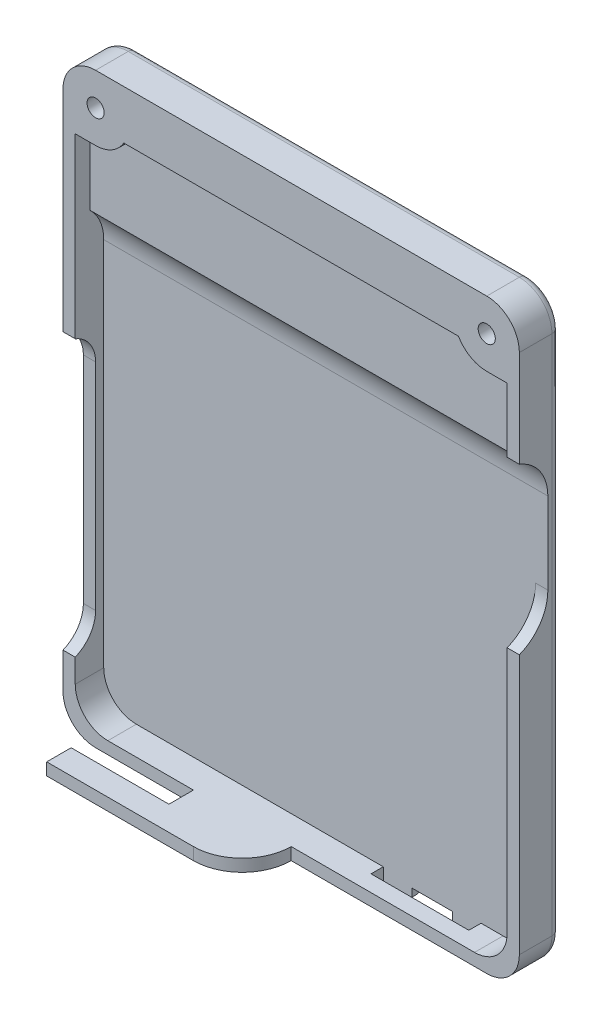
SolidWorks part; units mm, degrees
ref_plane "前视基准面" through (0, 0, 0) normal (0, 0, 1) x (1, 0, 0)
ref_plane "上视基准面" through (0, 0, 0) normal (0, 1, 0) x (1, 0, 0)
ref_plane "右视基准面" through (0, 0, 0) normal (1, 0, 0) x (0, 0, -1)
sketch "草图1" plane through (0, 0, 0) normal (0, 0, 1) x (1, 0, 0)
  line L0 (0, 0) -> (7.566, 0) construction
  line L1 (0, 0) -> (0, 23.6239) construction
  line L3 (0, 0) -> (-56, 0)
  line L4 (0, 0) -> (0, 72)
  line L5 (0, 72) -> (-56, 72)
  line L6 (-56, 0) -> (-56, 72)
  dimension "D1" = 56
  dimension "D2" = 72
extrude "凸台-拉伸1" add sketch "草图1" along normal blind 5
shell "抽壳1" thickness 1.5 removed face at (-28, 36, 5)
sketch "草图2" plane through (0, 0, 0) normal (0, 0, 1) x (1, 0, 0)
  line L0 (-54.5, 64) -> (-1.5, 64) construction
  line L1 (0, 72) -> (0, 68)
  line L2 (-56, 72) -> (-56, 68)
  line L4 (-54.5, 70.5) -> (-54.5, 1.5) construction
  line L5 (-56, 72) -> (-56, 0) construction
  line L7 (0, 0) -> (0, 72) construction
  line L8 (-56, 0) -> (-56, 72) construction
  line L9 (0, 72) -> (-56, 72)
  line L10 (-52, 64) -> (-54.5, 64)
  line L11 (-54.5, 64) -> (-54.5, 64.8775)
  line L13 (-52, 68) -> (-48, 68) construction
  line L14 (-48.5359, 66) -> (-7.4641, 66)
  line L15 (-28, 70) -> (-28, 60.4339) construction
  line L16 (-1.5, 64) -> (-1.5, 64.8775)
  line L17 (-4, 64) -> (-1.5, 64)
  arc A0 (-56, 68) -> (-54.5, 64.8775) centre (-52, 68) ccw
  circle A1 centre (-52, 68) radius 1.05
  arc A3 (0, 68) -> (-1.5, 64.8775) centre (-4, 68) cw
  circle A4 centre (-4, 68) radius 1.05
  arc A5 (-52, 64) -> (-48.5359, 66) centre (-52, 68) ccw
  arc A6 (-4, 64) -> (-7.4641, 66) centre (-4, 68) cw
  circle A7 centre (-52, 68) radius 1.7
  circle A8 centre (-4, 68) radius 1.7
  point P25 (-52, 72)
  point P27 (-3, 72)
  point P28 (-52, 64)
  point P29 (-4, 64)
  dimension "D2" = 2.1
  dimension "D1" = 3.4
  dimension "D3" = 6
extrude "凸台-拉伸2" add sketch "草图2" along normal blind 5 contours A5 L14 A6 L17 L16 A3 L1 L9 L2 A0 L11 L10
sketch "草图11" plane through (0, 0, 0) normal (1, 0, 0) x (0, 0, -1)
  line L0 (-13.6798, 44) -> (9.0258, 44) construction
  line L1 (-5, 64) -> (-1.5, 64) construction
  line L2 (0, 44) -> (-3.2, 44)
  line L3 (-3.2, 44) -> (-3.2, 72)
  line L4 (-3.2, 72) -> (0, 72)
  line L5 (0, 72) -> (0, 44)
  point P4 (-3.25, 64)
  point P7 (0, 0)
  point P12 (-1.5, 44)
  point P13 (-1.5, 44)
  dimension "D1" = 20
  dimension "D2" = 3.2
extrude "凸台-拉伸4" add sketch "草图11" against normal through all
extrude "切除-拉伸1" cut sketch "草图2<7>" along normal up to next contours A1 | A4
sketch "草图2<7>" plane through (0, 0, 0) normal (0, 0, 1) x (1, 0, 0) same geometry as "草图2"
extrude "切除-拉伸2" cut sketch "草图2<8>" along normal blind 2.5 contours A7 | A8
sketch "草图2<8>" plane through (0, 0, 0) normal (0, 0, 1) x (1, 0, 0) same geometry as "草图2"
sketch "草图8" plane through (-56, 0, 0) normal (-1, 0, 0) x (0, 0, 1)
  line L0 (2.5, 38.5009) -> (2.5, 12.0871)
  line L4 (5, 42.209) -> (5, 8.379)
  line L5 (5, 72) -> (5, 0) construction
  line L6 (5, 0) -> (0, 0) construction
  arc A0 (5, 8.379) -> (2.5, 12.0871) centre (6.5, 12.0871) cw
  arc A1 (5, 42.209) -> (2.5, 38.5009) centre (6.5, 38.5009) ccw
  point P8 (2.5, 25.294)
  point P9 (0, 0)
  dimension "D2" = 4
  dimension "D3" = 25.294
  dimension "D1" = 2.5
  dimension "D4" = 33.83
sketch "草图9" plane through (0, 0, 0) normal (1, 0, 0) x (0, 0, -1)
  line L0 (-1.5, 41) -> (-1.5, 51)
  line L1 (-5, 64) -> (-3.2, 64) construction
  line L2 (-5, 64) -> (1.8424, 64) construction
  line L3 (-5, 0) -> (-5, 72) construction
  line L4 (-12.5, 41) -> (-12.5, 51)
  line L5 (-7, 41) -> (-7, 51) construction
  line L6 (-5, 35.8765) -> (-5, 56.1235)
  arc A0 (-1.5, 51) -> (-12.5, 51) centre (-7, 51) ccw
  arc A1 (-12.5, 41) -> (-1.5, 41) centre (-7, 41) ccw
  point P13 (0, 0)
  point P14 (-5, 35.8765)
  point P15 (-5, 56.1235)
  point P18 (-7, 46)
  dimension "D5" = 5.5
  dimension "D1" = 18
  dimension "D2" = 2
  dimension "D3" = 10
  dimension "D4" = 5.5
sketch "草图10" plane through (0, 0, 0) normal (0, -1, 0) x (1, 0, 0)
  line L0 (-40, 5) -> (-40, 8)
  line L1 (-40, 8) -> (-52, 8)
  line L2 (-52, 8) -> (-52, 11)
  line L3 (-52, 11) -> (-34, 11)
  line L8 (0, 5) -> (0, 0) construction
  line L10 (-56, 5) -> (0, 5) construction
  line L11 (-16.7, 1.5) -> (-16.7, 0.5)
  line L12 (-20.2, 3) -> (-8.2, 3)
  line L13 (-20.2, 3) -> (-20.2, 1.5)
  line L14 (-20.2, 1.5) -> (-8.2, 1.5)
  line L15 (-8.2, 3) -> (-8.2, 1.5)
  line L16 (-16.7, 0.5) -> (-11.7, 0.5)
  line L17 (-11.7, 0.5) -> (-11.7, 1.5)
  line L19 (-28, 5) -> (-40, 5)
  line L23 (-56, 5) -> (-56, 0) construction
  arc A0 (-34, 11) -> (-28, 5) centre (-34, 5) cw
  point P7 (0, 0)
  point P8 (0, 0)
  point P9 (-25.5266, 5.2878)
  point P10 (0, 0)
  point P19 (-14.2, 0.5)
  point P22 (-14.2, 1.5)
  dimension "D2" = 18
  dimension "D3" = 28
  dimension "D4" = 3
  dimension "D5" = 3
  dimension "D6" = 8.2
  dimension "D7" = 2
  dimension "D8" = 1.5
  dimension "D9" = 12
  dimension "D10" = 5
  dimension "D11" = 1
  dimension "D12" = 16
extrude "凸台-拉伸3" add sketch "草图10" against normal blind 1.5 contours L0 L1 L2 L3 A0 L19
extrude "切除-拉伸3" cut sketch "草图10<3>" against normal up to next contours L12 L15 L14 L13
sketch "草图10<3>" plane through (0, 0, 0) normal (0, -1, 0) x (1, 0, 0) same geometry as "草图10"
extrude "切除-拉伸4" cut sketch "草图10<4>" against normal blind 1 and the other way through all contours L16 L17 L14 L11 region at (-14.2, 0, 1)
sketch "草图10<4>" plane through (0, 0, 0) normal (0, -1, 0) x (1, 0, 0) same geometry as "草图10"
extrude "切除-拉伸5" cut sketch "草图8" against normal up to next contours L0 A0 L4 A1
extrude "切除-拉伸6" cut sketch "草图9" against normal up to surface (54.5 mm away) contours A1 L0 A0 L4 up to face at (-54.5, 32.0176, 3.3267)
sketch "草图12" plane through (0, 0, 0) normal (1, 0, 0) x (0, 0, -1)
  line L0 (-1.5, 55.3301) -> (-1.5, 72)
  line L1 (-5, 72) -> (0, 72) construction
  line L2 (0, 72) -> (0, 68) construction
  line L3 (0, 51) -> (0, 72)
  line L4 (0, 72) -> (-1.5, 72)
  arc A0 (-1.5, 51) -> (-5, 56.1235) centre (-7, 51) ccw construction
  arc A1 (-1.5, 51) -> (-5, 56.1235) centre (-7, 51) ccw construction
  arc A2 (0, 51) -> (-1.5, 55.3301) centre (-7, 51) ccw
  arc A3 (0, 51) -> (-4.4545, 57.5208) centre (-7, 51) ccw construction
  point P12 (0.1455, 72)
  dimension "D2" = 1.5
  dimension "D1" = 1.5
fillet "圆角1" radius 4 4 edges at (-56, 0, 2.5) (0, 0, 2.5) (-56, 72, 2.5) (0, 72, 2.5)
fillet "圆角2" radius 4 2 edges at (-54.5, 1.5, 3.25) (-1.5, 1.5, 3.25)
fillet "圆角3" radius 1 10 edges at (-50.3, 68, 0) (-5.7, 68, 0) (-1.1716, 1.1716, 0) (0, 36, 0) (-1.1716, 70.8284, 0) (-28, 72, 0) (-54.8284, 70.8284, 0) (-56, 36, 0) (-54.8284, 1.1716, 0) (-28, 0, 0)
